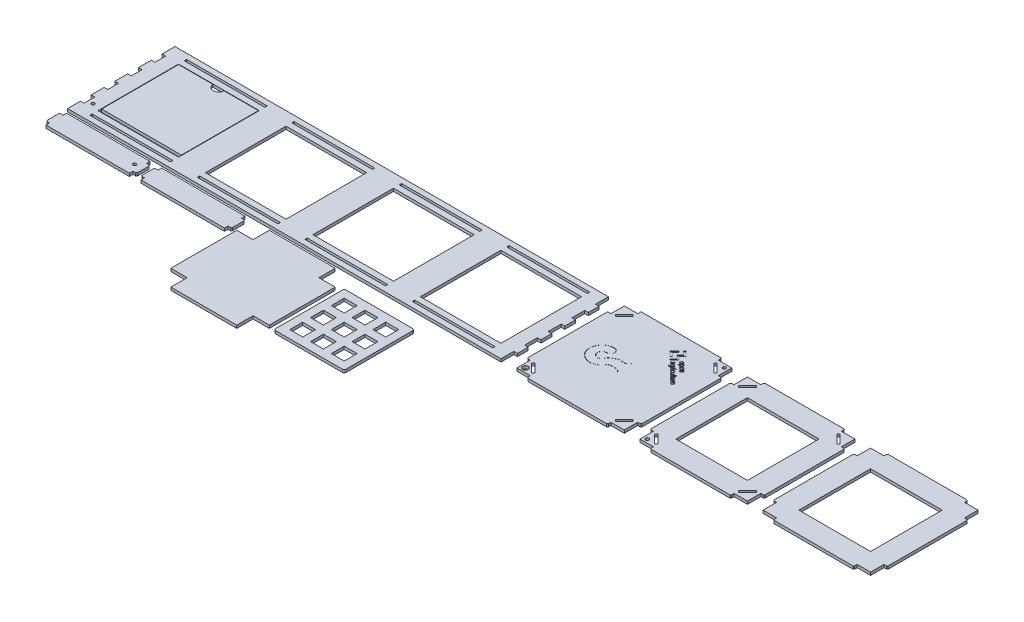
SolidWorks part; units mm, degrees
ref_plane "Front" through (0, 0, 0) normal (0, 0, 1) x (1, 0, 0)
ref_plane "Top" through (0, 0, 0) normal (0, 1, 0) x (1, 0, 0)
ref_plane "Right" through (0, 0, 0) normal (1, 0, 0) x (0, 0, -1)
sketch "Sketch1" plane through (0, 0, 0) normal (0, 1, 0) x (1, 0, 0)
  line L0 (0, 0) -> (228.6, 0) construction
  line L2 (-76.2, 76.2) -> (-76.2, -76.2) construction
  line L4 (76.2, 76.2) -> (76.2, -76.2) construction
  line L5 (-76.2, 76.2) -> (76.2, -76.2) construction
  line L6 (-76.2, -76.2) -> (76.2, 76.2) construction
  line L11 (76.2, 76.2) -> (228.6, 76.2)
  line L12 (76.2, 76.2) -> (76.2, -76.2) construction
  line L13 (76.2, -76.2) -> (228.6, -76.2)
  line L14 (228.6, 76.2) -> (228.6, -76.2) construction
  line L19 (-76.2, -76.2) -> (-228.6, -76.2)
  line L20 (-76.2, -76.2) -> (-76.2, 76.2) construction
  line L21 (-76.2, 76.2) -> (-228.6, 76.2)
  line L28 (76.2, -76.2) -> (-76.2, -76.2)
  line L34 (76.2, 76.2) -> (-76.2, 76.2)
  line L35 (-228.6, 76.2) -> (-228.6, -76.2) construction
  line L43 (-228.6, 76.2) -> (-381, 76.2)
  line L44 (-381, 76.2) -> (-381, -76.2) construction
  line L45 (-381, -76.2) -> (-228.6, -76.2)
  line L46 (228.6, 76.2) -> (228.6, 57.98)
  line L47 (228.6, 57.98) -> (233.68, 57.98)
  line L48 (233.68, 57.98) -> (233.68, 42.655)
  line L49 (233.68, 42.655) -> (228.6, 42.655)
  line L50 (228.6, 42.655) -> (228.6, 24.435)
  line L51 (228.6, 24.435) -> (233.68, 24.435)
  line L63 (233.68, 24.435) -> (233.68, 9.11)
  line L64 (233.68, 9.11) -> (228.6, 9.11)
  line L65 (228.6, 9.11) -> (228.6, -9.11)
  line L66 (228.6, -9.11) -> (233.68, -9.11)
  line L67 (233.68, -9.11) -> (233.68, -24.435)
  line L68 (233.68, -24.435) -> (228.6, -24.435)
  line L69 (228.6, -24.435) -> (228.6, -42.655)
  line L70 (228.6, -42.655) -> (233.68, -42.655)
  line L71 (233.68, -42.655) -> (233.68, -57.98)
  line L72 (233.68, -57.98) -> (228.6, -57.98)
  line L73 (228.6, -57.98) -> (228.6, -76.2)
  line L74 (-381, 76.2) -> (-386.08, 76.2)
  line L76 (-386.08, 57.9375) -> (-381, 57.9375)
  line L78 (-381, 42.6975) -> (-386.08, 42.6975)
  line L80 (-386.08, 24.3925) -> (-381, 24.3925)
  line L82 (-381, 9.1525) -> (-386.08, 9.1525)
  line L84 (-386.08, -9.1525) -> (-381, -9.1525)
  line L86 (-381, -24.3925) -> (-386.08, -24.3925)
  line L88 (-386.08, -42.6975) -> (-381, -42.6975)
  line L90 (-381, -57.9375) -> (-386.08, -57.9375)
  line L92 (-386.08, -76.2) -> (-381, -76.2)
  line L93 (233.68, 16.7725) -> (-381, 16.7725) construction
  line L94 (-381, 50.3175) -> (233.68, 50.3175) construction
  line L95 (-386.08, 76.2) -> (-386.08, 57.9375)
  line L96 (-386.08, 42.6975) -> (-386.08, 24.3925)
  line L97 (-381, 57.9375) -> (-381, 42.6975)
  line L98 (-381, 24.3925) -> (-381, 9.1525)
  line L99 (-381, -9.1525) -> (-381, -24.3925)
  line L100 (-381, -42.6975) -> (-381, -57.9375)
  line L101 (-381, -50.3175) -> (233.68, -50.3175) construction
  line L102 (-381, -16.7725) -> (233.68, -16.7725) construction
  line L103 (-386.08, 9.1525) -> (-386.08, -9.1525)
  line L104 (-386.08, -24.3925) -> (-386.08, -42.6975)
  line L105 (-386.08, -57.9375) -> (-386.08, -76.2)
  point P0 (0, 0)
  dimension "D2" = 152.4
  dimension "D1" = 152.4
  dimension "D3" = 5.08
  dimension "D5" = 15.24
  dimension "D4" = 15.325
extrude "Boss-Extrude1" add sketch "Sketch1" along normal blind 4.064
sketch "Sketch4" plane through (0, 4.064, 0) normal (0, 1, 0) x (1, 0, 0)
  line L0 (-228.6, 76.2) -> (-228.6, -76.2) construction
  line L1 (-228.6, 76.2) -> (-228.6, -76.2)
  line L2 (-76.2, 76.2) -> (-76.2, -76.2) construction
  line L3 (-76.2, 76.2) -> (-76.2, -76.2)
  line L4 (76.2, 76.2) -> (76.2, -76.2) construction
  line L5 (76.2, 76.2) -> (76.2, -76.2)
sketch "Sketch5" plane through (0, 4.064, 0) normal (0, 1, 0) x (1, 0, 0)
  line L0 (-381, -9.1525) -> (-381, 9.1525) construction
  line L1 (-228.6, 0) -> (-381, 0) construction
  line L2 (-228.6, 76.2) -> (-228.6, -76.2) construction
  line L3 (-228.6, 0) -> (-76.2, 0) construction
  line L4 (-76.2, 76.2) -> (-76.2, -76.2) construction
  line L5 (-76.2, 0) -> (76.2, 0) construction
  line L6 (76.2, 76.2) -> (76.2, -76.2) construction
  line L7 (76.2, 0) -> (228.6, 0) construction
  line L8 (228.6, -9.11) -> (228.6, 9.11) construction
  line L9 (-304.8, 0) -> (-304.8, -76.2) construction
  line L10 (-386.08, -76.2) -> (228.6, -76.2) construction
  line L11 (-152.4, 0) -> (-152.4, -76.2) construction
  line L12 (0, 0) -> (0, -76.2) construction
  line L13 (152.4, 0) -> (152.4, -76.2) construction
  line L14 (-247.65, -68.58) -> (-247.65, -76.2) construction
  line L15 (-361.95, -65.278) -> (-247.65, -65.278)
  line L16 (-361.95, -65.278) -> (-361.95, -68.58)
  line L17 (-361.95, -68.58) -> (-247.65, -68.58)
  line L18 (-247.65, -65.278) -> (-247.65, -68.58)
  line L19 (-361.95, -65.278) -> (-247.65, -68.58) construction
  line L20 (-361.95, -68.58) -> (-247.65, -65.278) construction
  line L21 (-209.55, -65.278) -> (-95.25, -65.278)
  line L22 (-209.55, -65.278) -> (-209.55, -68.58)
  line L23 (-209.55, -68.58) -> (-95.25, -68.58)
  line L24 (-95.25, -65.278) -> (-95.25, -68.58)
  line L25 (-209.55, -65.278) -> (-95.25, -68.58) construction
  line L26 (-209.55, -68.58) -> (-95.25, -65.278) construction
  line L27 (-57.15, -68.58) -> (57.15, -68.58)
  line L28 (-57.15, -68.58) -> (-57.15, -65.278)
  line L29 (-57.15, -65.278) -> (57.15, -65.278)
  line L30 (57.15, -68.58) -> (57.15, -65.278)
  line L31 (-57.15, -68.58) -> (57.15, -65.278) construction
  line L32 (-57.15, -65.278) -> (57.15, -68.58) construction
  line L33 (95.25, -68.58) -> (209.55, -68.58)
  line L34 (95.25, -68.58) -> (95.25, -65.278)
  line L35 (95.25, -65.278) -> (209.55, -65.278)
  line L36 (209.55, -68.58) -> (209.55, -65.278)
  line L37 (95.25, -68.58) -> (209.55, -65.278) construction
  line L38 (95.25, -65.278) -> (209.55, -68.58) construction
  line L39 (95.25, 65.278) -> (209.55, 68.58) construction
  line L40 (95.25, 68.58) -> (209.55, 65.278) construction
  line L41 (-57.15, 65.278) -> (57.15, 68.58) construction
  line L42 (-57.15, 68.58) -> (57.15, 65.278) construction
  line L43 (-209.55, 68.58) -> (-95.25, 65.278) construction
  line L44 (-209.55, 65.278) -> (-95.25, 68.58) construction
  line L45 (-361.95, 68.58) -> (-247.65, 65.278) construction
  line L46 (-361.95, 65.278) -> (-247.65, 68.58) construction
  line L47 (-247.65, 68.58) -> (-247.65, 76.2) construction
  line L48 (209.55, 68.58) -> (209.55, 65.278)
  line L49 (95.25, 65.278) -> (209.55, 65.278)
  line L50 (95.25, 68.58) -> (95.25, 65.278)
  line L51 (95.25, 68.58) -> (209.55, 68.58)
  line L52 (57.15, 68.58) -> (57.15, 65.278)
  line L53 (-57.15, 65.278) -> (57.15, 65.278)
  line L54 (-57.15, 68.58) -> (-57.15, 65.278)
  line L55 (-57.15, 68.58) -> (57.15, 68.58)
  line L56 (-95.25, 65.278) -> (-95.25, 68.58)
  line L57 (-209.55, 68.58) -> (-95.25, 68.58)
  line L58 (-209.55, 65.278) -> (-209.55, 68.58)
  line L59 (-209.55, 65.278) -> (-95.25, 65.278)
  line L60 (-247.65, 65.278) -> (-247.65, 68.58)
  line L61 (-361.95, 68.58) -> (-247.65, 68.58)
  line L62 (-361.95, 65.278) -> (-361.95, 68.58)
  line L63 (-361.95, 65.278) -> (-247.65, 65.278)
  line L64 (228.6, 76.2) -> (-386.08, 76.2) construction
  line L65 (-361.95, 57.15) -> (-247.65, 57.15)
  line L66 (-361.95, 57.15) -> (-361.95, -57.15)
  line L67 (-361.95, -57.15) -> (-247.65, -57.15)
  line L68 (-247.65, 57.15) -> (-247.65, -57.15)
  line L69 (-361.95, 57.15) -> (-247.65, -57.15) construction
  line L70 (-361.95, -57.15) -> (-247.65, 57.15) construction
  line L71 (-209.55, 57.15) -> (-95.25, 57.15)
  line L72 (-209.55, 57.15) -> (-209.55, -57.15)
  line L73 (-209.55, -57.15) -> (-95.25, -57.15)
  line L74 (-95.25, 57.15) -> (-95.25, -57.15)
  line L75 (-209.55, 57.15) -> (-95.25, -57.15) construction
  line L76 (-209.55, -57.15) -> (-95.25, 57.15) construction
  line L77 (-57.15, 57.15) -> (57.15, 57.15)
  line L78 (-57.15, 57.15) -> (-57.15, -57.15)
  line L79 (-57.15, -57.15) -> (57.15, -57.15)
  line L80 (57.15, 57.15) -> (57.15, -57.15)
  line L81 (-57.15, 57.15) -> (57.15, -57.15) construction
  line L82 (-57.15, -57.15) -> (57.15, 57.15) construction
  line L83 (95.25, 57.15) -> (209.55, 57.15)
  line L84 (95.25, 57.15) -> (95.25, -57.15)
  line L85 (95.25, -57.15) -> (209.55, -57.15)
  line L86 (209.55, 57.15) -> (209.55, -57.15)
  line L87 (95.25, 57.15) -> (209.55, -57.15) construction
  line L88 (95.25, -57.15) -> (209.55, 57.15) construction
  circle A0 centre (-373.95, -52.15) radius 2.2225
  point P27 (-304.8, -66.929)
  point P32 (-152.4, -66.929)
  point P37 (0, -66.929)
  point P42 (152.4, -66.929)
  point P66 (152.4, 66.929)
  point P67 (0, 66.929)
  point P68 (-152.4, 66.929)
  point P69 (-304.8, 66.929)
  dimension "D5" = 4.445
  dimension "D7" = 5
  dimension "D1" = 7.62
  dimension "D2" = 3.302
  dimension "D3" = 114.3
  dimension "D4" = 19.05
  dimension "D6" = 12
  dimension "D8" = 19.05
extrude "Cut-Extrude2" cut sketch "Sketch5" against normal through all
sketch "Sketch6" plane through (0, 0, 0) normal (0, 1, 0) x (1, 0, 0)
  line L0 (0, 0) -> (327.3425, 0) construction
  line L1 (327.3425, 0) -> (327.3425, 78.5813) construction
  line L2 (251.1425, 76.2) -> (403.5425, 76.2) construction
  line L3 (251.1425, 76.2) -> (251.1425, -76.2) construction
  line L4 (251.1425, -76.2) -> (403.5425, -76.2) construction
  line L5 (403.5425, 76.2) -> (403.5425, -76.2) construction
  line L6 (251.1425, 76.2) -> (403.5425, -76.2) construction
  line L7 (251.1425, -76.2) -> (403.5425, 76.2) construction
  line L8 (327.3425, 0) -> (405.9238, 0) construction
  line L9 (327.3425, 0) -> (327.3425, -78.5813) construction
  line L10 (251.1425, 57.185) -> (251.1425, 76.2)
  line L11 (270.1575, 80.9625) -> (384.5275, 80.9625)
  line L12 (270.1575, 80.9625) -> (270.1575, 76.2)
  line L13 (270.1575, 76.2) -> (384.5275, 76.2) construction
  line L14 (384.5275, 80.9625) -> (384.5275, 76.2)
  line L15 (270.1575, 80.9625) -> (384.5275, 76.2) construction
  line L16 (270.1575, 76.2) -> (384.5275, 80.9625) construction
  line L17 (408.305, -57.185) -> (403.5425, -57.185)
  line L18 (408.305, -57.185) -> (408.305, 57.185)
  line L19 (408.305, 57.185) -> (403.5425, 57.185)
  line L20 (403.5425, -57.185) -> (403.5425, 57.185) construction
  line L21 (408.305, -57.185) -> (403.5425, 57.185) construction
  line L22 (408.305, 57.185) -> (403.5425, -57.185) construction
  line L23 (270.1575, -80.9625) -> (384.5275, -80.9625)
  line L24 (270.1575, -80.9625) -> (270.1575, -76.2)
  line L25 (270.1575, -76.2) -> (384.5275, -76.2) construction
  line L26 (384.5275, -80.9625) -> (384.5275, -76.2)
  line L27 (270.1575, -80.9625) -> (384.5275, -76.2) construction
  line L28 (270.1575, -76.2) -> (384.5275, -80.9625) construction
  line L29 (246.38, 57.185) -> (251.1425, 57.185)
  line L30 (246.38, 57.185) -> (246.38, -57.185)
  line L31 (246.38, -57.185) -> (251.1425, -57.185)
  line L32 (251.1425, 57.185) -> (251.1425, -57.185) construction
  line L33 (246.38, 57.185) -> (251.1425, -57.185) construction
  line L34 (246.38, -57.185) -> (251.1425, 57.185) construction
  line L35 (251.1425, 76.2) -> (270.1575, 76.2)
  line L36 (384.5275, 76.2) -> (403.5425, 76.2)
  line L37 (403.5425, 76.2) -> (403.5425, 57.185)
  line L38 (403.5425, -57.185) -> (403.5425, -76.2)
  line L39 (403.5425, -76.2) -> (384.5275, -76.2)
  line L40 (270.1575, -76.2) -> (251.1425, -76.2)
  line L41 (251.1425, -76.2) -> (251.1425, -57.185)
  line L42 (421.005, 57.185) -> (421.005, -57.185)
  line L43 (421.005, 57.185) -> (425.7675, 57.185)
  line L44 (425.7675, 57.185) -> (425.7675, 76.2)
  line L45 (425.7675, 76.2) -> (444.7825, 76.2)
  line L46 (444.7825, 80.9625) -> (444.7825, 76.2)
  line L47 (444.7825, 80.9625) -> (559.1525, 80.9625)
  line L48 (559.1525, 80.9625) -> (559.1525, 76.2)
  line L49 (559.1525, 76.2) -> (578.1675, 76.2)
  line L50 (578.1675, 76.2) -> (578.1675, 57.185)
  line L51 (582.93, 57.185) -> (578.1675, 57.185)
  line L52 (582.93, -57.185) -> (582.93, 57.185)
  line L53 (582.93, -57.185) -> (578.1675, -57.185)
  line L54 (578.1675, -57.185) -> (578.1675, -76.2)
  line L55 (578.1675, -76.2) -> (559.1525, -76.2)
  line L56 (559.1525, -80.9625) -> (559.1525, -76.2)
  line L57 (444.7825, -80.9625) -> (559.1525, -80.9625)
  line L58 (444.7825, -80.9625) -> (444.7825, -76.2)
  line L59 (444.7825, -76.2) -> (425.7675, -76.2)
  line L60 (425.7675, -76.2) -> (425.7675, -57.185)
  line L61 (421.005, -57.185) -> (425.7675, -57.185)
  line L62 (425.7675, 76.2) -> (578.1675, -76.2) construction
  line L63 (595.63, 57.185) -> (595.63, -57.185)
  line L64 (595.63, 57.185) -> (600.3925, 57.185)
  line L65 (600.3925, 57.185) -> (600.3925, 76.2)
  line L66 (600.3925, 76.2) -> (619.4075, 76.2)
  line L67 (619.4075, 80.9625) -> (619.4075, 76.2)
  line L68 (619.4075, 80.9625) -> (733.7775, 80.9625)
  line L69 (733.7775, 80.9625) -> (733.7775, 76.2)
  line L70 (733.7775, 76.2) -> (752.7925, 76.2)
  line L71 (752.7925, 76.2) -> (752.7925, 57.185)
  line L72 (757.555, 57.185) -> (752.7925, 57.185)
  line L73 (757.555, -57.185) -> (757.555, 57.185)
  line L74 (757.555, -57.185) -> (752.7925, -57.185)
  line L75 (752.7925, -57.185) -> (752.7925, -76.2)
  line L76 (752.7925, -76.2) -> (733.7775, -76.2)
  line L77 (733.7775, -80.9625) -> (733.7775, -76.2)
  line L78 (619.4075, -80.9625) -> (733.7775, -80.9625)
  line L79 (619.4075, -80.9625) -> (619.4075, -76.2)
  line L80 (619.4075, -76.2) -> (600.3925, -76.2)
  line L81 (600.3925, -76.2) -> (600.3925, -57.185)
  line L82 (595.63, -57.185) -> (600.3925, -57.185)
  line L83 (600.3925, 76.2) -> (752.7925, -76.2) construction
  line L84 (451.1675, 50.8) -> (552.7675, 50.8)
  line L85 (451.1675, 50.8) -> (451.1675, -50.8)
  line L86 (451.1675, -50.8) -> (552.7675, -50.8)
  line L87 (552.7675, 50.8) -> (552.7675, -50.8)
  line L88 (451.1675, 50.8) -> (552.7675, -50.8) construction
  line L89 (451.1675, -50.8) -> (552.7675, 50.8) construction
  line L90 (233.68, -24.435) -> (233.68, -9.11) construction
  line L91 (727.3925, 50.8) -> (625.7925, 50.8)
  line L92 (727.3925, 50.8) -> (727.3925, -50.8)
  line L93 (727.3925, -50.8) -> (625.7925, -50.8)
  line L94 (625.7925, 50.8) -> (625.7925, -50.8)
  line L95 (727.3925, 50.8) -> (625.7925, -50.8) construction
  line L96 (727.3925, -50.8) -> (625.7925, 50.8) construction
  line L97 (-76.2, -57.15) -> (76.2, -57.15) construction
  line L98 (-76.2, 76.2) -> (-76.2, -76.2) construction
  line L99 (76.2, 76.2) -> (76.2, -76.2) construction
  line L100 (76.2, -57.15) -> (228.6, -57.15) construction
  line L101 (228.6, -76.2) -> (228.6, -57.98) construction
  line L102 (-57.15, -57.15) -> (57.15, -57.15) construction
  line L103 (95.25, 57.15) -> (209.55, 57.15) construction
  point P22 (248.7613, 0)
  point P67 (501.9675, 0)
  point P72 (676.5925, 0)
  dimension "D3" = 4.7625
  dimension "D7" = 12.7
  dimension "D8" = 101.6
  dimension "D5" = 12.7
  dimension "D1" = 114.3
  dimension "D2" = 114.37
  dimension "D6" = 3
extrude "Boss-Extrude2" add sketch "Sketch6" along normal blind 4.064 separate body
sketch "Sketch7" plane through (0, 0, 0) normal (0, 1, 0) x (1, 0, 0)
  line L0 (-361.95, 65.278) -> (-361.95, -53.086) construction
  line L1 (-381.08, -82.55) -> (-262.716, -82.55)
  line L2 (-381.08, -82.55) -> (-381.08, -87.63)
  line L3 (-381.08, -111.76) -> (-262.716, -111.76)
  line L4 (-262.716, -82.55) -> (-262.716, -87.63)
  line L5 (-381.08, -82.55) -> (-262.716, -111.76) construction
  line L6 (-381.08, -111.76) -> (-262.716, -82.55) construction
  line L7 (-361.95, 57.15) -> (-361.95, -57.15) construction
  line L8 (-361.95, -53.086) -> (-361.95, -57.15) construction
  line L9 (251.1425, -57.185) -> (251.1425, -76.2) construction
  line L10 (251.1425, -76.2) -> (270.1575, -76.2) construction
  line L12 (-381.08, -87.63) -> (-386.08, -87.63)
  line L13 (257.5967, -57.1734) -> (270.1691, -69.7458) construction
  line L14 (257.5967, -57.1734) -> (255.2618, -59.5083) construction
  line L15 (255.2618, -59.5083) -> (267.8342, -72.0807) construction
  line L16 (270.1691, -69.7458) -> (267.8342, -72.0807) construction
  line L17 (257.5967, -57.1734) -> (267.8342, -72.0807) construction
  line L18 (255.2618, -59.5083) -> (270.1691, -69.7458) construction
  line L19 (-386.08, -87.63) -> (-386.08, -106.68)
  line L20 (-386.08, -106.68) -> (-381.08, -106.68)
  line L22 (262.7155, -64.627) -> (260.65, -66.6925) construction
  line L23 (-381.08, -106.68) -> (-381.08, -111.76)
  line L24 (-262.716, -87.63) -> (-257.716, -87.63)
  line L25 (-257.716, -87.63) -> (-257.716, -106.68)
  line L26 (-257.716, -106.68) -> (-262.716, -106.68)
  line L27 (-262.716, -106.68) -> (-262.716, -111.76)
  line L28 (-386.08, -76.2) -> (228.6, -76.2) construction
  line L29 (-386.08, -57.9375) -> (-386.08, -76.2) construction
  line L30 (-246.366, -82.55) -> (-128.002, -82.55)
  line L31 (-246.366, -82.55) -> (-246.366, -87.63)
  line L32 (-246.366, -111.76) -> (-128.002, -111.76)
  line L33 (-128.002, -82.55) -> (-128.002, -87.63)
  line L34 (-246.366, -87.63) -> (-251.366, -87.63)
  line L35 (-251.366, -87.63) -> (-251.366, -106.68)
  line L36 (-251.366, -106.68) -> (-246.366, -106.68)
  line L37 (-246.366, -106.68) -> (-246.366, -111.76)
  line L38 (-128.002, -87.63) -> (-123.002, -87.63)
  line L39 (-123.002, -87.63) -> (-123.002, -106.68)
  line L40 (-123.002, -106.68) -> (-128.002, -106.68)
  line L41 (-128.002, -106.68) -> (-128.002, -111.76)
  line L42 (-246.366, -82.55) -> (-128.002, -111.76) construction
  line L43 (-246.366, -111.76) -> (-128.002, -82.55) construction
  line L44 (-361.95, 65.278) -> (-386.08, 65.278) construction
  line L45 (-386.08, 76.2) -> (-386.08, 57.9375) construction
  line L46 (251.1425, -57.185) -> (270.1575, -76.2) construction
  point P0 (-321.898, -97.155)
  point P14 (262.7155, -64.627)
  point P38 (-187.184, -97.155)
  dimension "D1" = 29.21
  dimension "D2" = 4.064
  dimension "D3" = 3.302
  dimension "D4" = 19.05
  dimension "D5" = 17.78
  dimension "D6" = 5
  dimension "D7" = 6.35
  dimension "D9" = 6.35
  dimension "D10" = 1.27
  dimension "D8" = 2
extrude "PILLAR POSITION" add sketch "Sketch7" along normal blind 4.064 separate body
sketch "Sketch8" plane through (0, 4.064, 0) normal (0, 1, 0) x (1, 0, 0)
  line L0 (255.2618, -59.5083) -> (267.8342, -72.0807) construction
  line L1 (270.1691, -69.7458) -> (267.8342, -72.0807) construction
  line L2 (257.5967, -57.1734) -> (270.1691, -69.7458) construction
  line L3 (257.5967, -57.1734) -> (255.2618, -59.5083) construction
  line L4 (255.2618, -59.5083) -> (267.8342, -72.0807)
  line L5 (270.1691, -69.7458) -> (267.8342, -72.0807)
  line L6 (257.5967, -57.1734) -> (270.1691, -69.7458)
  line L7 (257.5967, -57.1734) -> (255.2618, -59.5083)
  line L8 (251.1425, 76.2) -> (403.5425, -76.2) construction
  line L9 (270.1691, 69.7458) -> (257.5967, 57.1734)
  line L10 (270.1691, 69.7458) -> (267.8342, 72.0807)
  line L11 (267.8342, 72.0807) -> (255.2618, 59.5083)
  line L12 (257.5967, 57.1734) -> (255.2618, 59.5083)
  line L13 (397.0883, 57.1734) -> (384.5159, 69.7458)
  line L14 (397.0883, 57.1734) -> (399.4232, 59.5083)
  line L15 (399.4232, 59.5083) -> (386.8508, 72.0807)
  line L16 (384.5159, 69.7458) -> (386.8508, 72.0807)
  line L17 (384.5159, -69.7458) -> (397.0883, -57.1734)
  line L18 (384.5159, -69.7458) -> (386.8508, -72.0807)
  line L19 (386.8508, -72.0807) -> (399.4232, -59.5083)
  line L20 (397.0883, -57.1734) -> (399.4232, -59.5083)
  line L21 (425.7675, -57.185) -> (444.7825, -76.2) construction
  line L22 (429.8868, -59.5083) -> (432.2217, -57.1734)
  line L23 (432.2217, -57.1734) -> (444.7941, -69.7458)
  line L24 (444.7941, -69.7458) -> (442.4592, -72.0807)
  line L25 (435.275, -66.6925) -> (438.5079, -63.4596) construction
  line L26 (429.8868, -59.5083) -> (442.4592, -72.0807)
  line L27 (425.7675, 76.2) -> (578.1675, -76.2) construction
  line L28 (432.2217, 57.1734) -> (429.8868, 59.5083)
  line L29 (442.4592, 72.0807) -> (429.8868, 59.5083)
  line L30 (442.4592, 72.0807) -> (444.7941, 69.7458)
  line L31 (444.7941, 69.7458) -> (432.2217, 57.1734)
  line L32 (559.1409, 69.7458) -> (561.4758, 72.0807)
  line L33 (574.0482, 59.5083) -> (561.4758, 72.0807)
  line L34 (574.0482, 59.5083) -> (571.7133, 57.1734)
  line L35 (571.7133, 57.1734) -> (559.1409, 69.7458)
  line L36 (571.7133, -57.1734) -> (574.0482, -59.5083)
  line L37 (561.4758, -72.0807) -> (574.0482, -59.5083)
  line L38 (561.4758, -72.0807) -> (559.1409, -69.7458)
  line L39 (559.1409, -69.7458) -> (571.7133, -57.1734)
  line L40 (251.1425, -57.185) -> (270.1575, -76.2) construction
  line L41 (261.548, -65.7945) -> (260.65, -66.6925) construction
  line L42 (442.4592, -72.0807) -> (441.5612, -72.9787) construction
  circle A0 centre (327.3425, 0) radius 20.7898 construction
  circle A1 centre (327.3425, 0) radius 20.7898 construction
  circle A2 centre (327.3425, 0) radius 20.7898 construction
  circle A3 centre (327.3425, 0) radius 20.7898 construction
  circle A4 centre (501.9675, 0) radius 71.842 construction
  point P28 (327.3425, 0)
  point P58 (501.9675, 0)
  dimension "D1" = 4
  dimension "D2" = 4
extrude "Cut-Extrude3" cut sketch "Sketch8" against normal through all
sketch "Sketch10" plane through (0, 4.064, 0) normal (0, 1, 0) x (1, 0, 0)
  line L0 (-247.65, 57.15) -> (-361.95, 57.15) construction
  line L1 (-95.25, 57.15) -> (-209.55, 57.15) construction
  line L2 (57.15, 57.15) -> (-57.15, 57.15) construction
  line L3 (209.55, 57.15) -> (95.25, 57.15) construction
  line L4 (-296.8, 57.15) -> (-312.8, 57.15)
  line L5 (-144.4, 57.15) -> (-160.4, 57.15)
  line L6 (8, 57.15) -> (-8, 57.15)
  line L7 (160.4, 57.15) -> (144.4, 57.15)
  line L8 (-361.95, -53.086) -> (-247.65, -53.086)
  line L9 (-304.8, -53.086) -> (-304.8, -57.15) construction
  line L14 (-361.95, 57.15) -> (-361.95, -57.15) construction
  line L15 (-247.65, -57.15) -> (-247.65, 57.15) construction
  line L16 (-361.95, -57.15) -> (-247.65, -57.15) construction
  line L17 (-209.55, -53.086) -> (-95.25, -53.086)
  line L18 (-209.55, 57.15) -> (-209.55, -57.15) construction
  line L19 (-95.25, -57.15) -> (-95.25, 57.15) construction
  line L20 (-57.15, -53.086) -> (57.15, -53.086)
  line L21 (-57.15, 57.15) -> (-57.15, -57.15) construction
  line L22 (57.15, -57.15) -> (57.15, 57.15) construction
  line L23 (95.25, -53.086) -> (209.55, -53.086)
  line L24 (95.25, 57.15) -> (95.25, -57.15) construction
  line L25 (209.55, -57.15) -> (209.55, 57.15) construction
  line L27 (-361.95, 57.15) -> (-361.95, -53.086) construction
  arc A0 (-312.8, 57.15) -> (-296.8, 57.15) centre (-304.8, 57.15) ccw
  arc A1 (-160.4, 57.15) -> (-144.4, 57.15) centre (-152.4, 57.15) ccw
  arc A2 (-8, 57.15) -> (8, 57.15) centre (0, 57.15) ccw
  arc A3 (144.4, 57.15) -> (160.4, 57.15) centre (152.4, 57.15) ccw
  dimension "D1" = 16
  dimension "D2" = 4.064
sketch "Sketch18" plane through (0, 4.064, 0) normal (0, 1, 0) x (1, 0, 0)
  line L0 (-361.95, 57.15) -> (-247.65, -53.086) construction
  line L6 (-247.65, 57.15) -> (-361.95, 57.15) construction
  line L7 (-361.3901, 56.61) -> (-312.7818, 56.61)
  line L9 (-361.3901, 56.61) -> (-361.3901, -52.546)
  line L10 (-361.3901, -52.546) -> (-248.2099, -52.546)
  line L11 (-248.2099, 56.61) -> (-248.2099, -52.546)
  line L12 (-361.3901, 56.61) -> (-248.2099, -52.546) construction
  line L13 (-361.3901, -52.546) -> (-248.2099, 56.61) construction
  line L14 (-296.8182, 56.61) -> (-248.2099, 56.61)
  arc A2 (-312.8, 57.15) -> (-296.8, 57.15) centre (-304.8, 57.15) ccw construction
  arc A3 (-312.7818, 56.61) -> (-296.8182, 56.61) centre (-304.8, 57.15) ccw
  point P4 (-304.8, 2.032)
  dimension "D1" = 0.54
extrude "Boss-Extrude8" add sketch "Sketch18" against normal blind 4.064 separate body
sketch "Sketch11" plane through (0, 0, 0) normal (0, 1, 0) x (1, 0, 0)
  line L0 (-209.55, -57.15) -> (-209.55, -65.278) construction
  line L5 (-93.538, -105.664) -> (-0.066, -105.664) construction
  line L6 (-93.538, -105.664) -> (-93.538, -199.136) construction
  line L7 (-93.538, -199.136) -> (-0.066, -199.136) construction
  line L8 (-0.066, -105.664) -> (-0.066, -199.136) construction
  line L9 (-93.538, -105.664) -> (-0.066, -199.136) construction
  line L10 (-93.538, -199.136) -> (-0.066, -105.664) construction
  line L11 (-93.538, -105.664) -> (-116.652, -105.664)
  line L12 (-116.652, -105.664) -> (-116.652, -199.136)
  line L13 (-116.652, -199.136) -> (-93.538, -199.136)
  line L14 (-93.538, -105.664) -> (-93.538, -82.55)
  line L15 (-93.538, -82.55) -> (-0.066, -82.55)
  line L16 (-0.066, -82.55) -> (-0.066, -105.664)
  line L17 (-0.066, -105.664) -> (23.048, -105.664)
  line L18 (23.048, -105.664) -> (23.048, -199.136)
  line L19 (23.048, -199.136) -> (-0.066, -199.136)
  line L20 (-0.066, -199.136) -> (-0.066, -222.25)
  line L21 (-0.066, -222.25) -> (-93.538, -222.25)
  line L22 (-93.538, -222.25) -> (-93.538, -199.136)
  line L23 (-386.08, -76.2) -> (228.6, -76.2) construction
  line L24 (-123.002, -106.68) -> (-123.002, -87.63) construction
  line L25 (-209.55, -57.15) -> (-95.25, -57.15) construction
  line L26 (451.1675, -50.8) -> (552.7675, -50.8) construction
  line L27 (209.55, -53.086) -> (209.55, -76.2) construction
  line L28 (-97.602, -219.71) -> (3.998, -219.71) construction
  line L29 (-46.802, -152.4) -> (-46.802, -219.71) construction
  line L30 (-97.602, -219.71) -> (-97.602, -222.25) construction
  line L31 (-97.602, -222.25) -> (-93.538, -222.25) construction
  line L32 (-0.066, -222.25) -> (3.998, -222.25) construction
  line L33 (3.998, -222.25) -> (3.998, -219.71) construction
  point P0 (-46.802, -152.4)
  point P33 (-46.802, -219.71)
  dimension "D1" = 4.064
  dimension "D2" = 101.6
  dimension "D3" = 101.6
  dimension "D4" = 6.35
  dimension "D5" = 6.35
  dimension "D6" = 2.54
extrude "Boss-Extrude5" add sketch "Sketch11" along normal blind 4.064 separate body
sketch "Sketch12" plane through (0, 4.064, 0) normal (0, 1, 0) x (1, 0, 0)
  line L0 (-93.538, -105.664) -> (-0.066, -105.664)
  line L1 (-0.066, -105.664) -> (-0.066, -199.136)
  line L2 (-0.066, -199.136) -> (-93.538, -199.136)
  line L3 (-93.538, -105.664) -> (-93.538, -199.136)
sketch "Sketch13" plane through (0, 0, 0) normal (0, 1, 0) x (1, 0, 0)
  line L16 (-223.9443, 14.6616) -> (-211.1797, 14.6616)
  line L17 (-211.1797, 14.6616) -> (-211.1797, 5.1786)
  line L18 (-211.1797, 5.1786) -> (-201.7193, 5.1786)
  line L19 (350.3041, 64.4565) -> (356.7512, 58.0094)
  line L20 (356.7512, 58.0094) -> (351.9616, 53.2197)
  line L21 (351.9616, 53.2197) -> (356.7398, 48.4415)
  line L22 (356.7398, 48.4415) -> (350.2812, 41.983)
  line L24 (348.6694, 43.5948) -> (353.4934, 48.4187)
  line L25 (353.4934, 48.4187) -> (348.7266, 53.1854)
  line L26 (348.7266, 53.1854) -> (353.5391, 57.9979)
  line L27 (353.5391, 57.9979) -> (348.6923, 62.8447)
  line L28 (348.6923, 62.8447) -> (350.3041, 64.4565)
  line L29 (345.5145, 59.6669) -> (347.1377, 58.0437)
  line L30 (347.1377, 58.0437) -> (342.3023, 53.2083)
  line L31 (342.3023, 53.2083) -> (347.1262, 48.3844)
  line L32 (347.1262, 48.3844) -> (345.503, 46.7612)
  line L33 (345.503, 46.7612) -> (339.0559, 53.2083)
  line L34 (339.0559, 53.2083) -> (345.5145, 59.6669)
  line L36 (350.7409, 41.9187) -> (377.6929, 14.9667) construction
  line L37 (358.5912, 47.064) -> (396.3306, 9.3246) construction
  line L38 (348.6694, 43.5948) -> (350.2812, 41.983)
  line L41 (-201.7193, 5.1786) -> (-201.7193, -7.6086)
  line L43 (-204.9105, -7.6086) -> (-204.9105, 1.9422)
  line L44 (-204.9105, 1.9422) -> (-214.3482, 1.9422)
  line L45 (-214.3482, 1.9422) -> (-214.3482, 11.4705)
  line L46 (-214.3482, 11.4705) -> (-223.9443, 11.4705)
  line L47 (-223.9443, 11.4705) -> (-223.9443, 14.6616)
  line L48 (-223.9443, 5.1786) -> (-220.7305, 5.1786)
  line L49 (-220.7305, 5.1786) -> (-220.7305, -4.3949)
  line L50 (-220.7305, -4.3949) -> (-211.1797, -4.3949)
  line L51 (-211.1797, -4.3949) -> (-211.1797, -7.6086)
  line L52 (-211.1797, -7.6086) -> (-223.9443, -7.6086)
  line L53 (-223.9443, -7.6086) -> (-223.9443, 5.1786)
  line L54 (-200.854, -7.608) -> (-149.188, -7.608) construction
  line L55 (-361.95, 57.15) -> (-247.65, -53.086) construction
  line L56 (-204.9105, -7.6086) -> (-201.7193, -7.6086)
  line L57 (-200.854, -7.608) -> (-200.854, 5.1786) construction
  line L58 (-200.854, 5.1786) -> (-201.7193, 5.1786) construction
  line L59 (-200.854, 1.9422) -> (-182.9615, 1.9422) construction
  line L60 (-200.854, -2.3557) -> (-181.4784, -2.3557) construction
  line L61 (-361.95, 57.15) -> (-361.95, -57.15) construction
  line L62 (-273.05, 31.75) -> (-336.55, 31.75) construction
  line L63 (-273.05, 31.75) -> (-273.05, -27.686) construction
  line L64 (-273.05, -27.686) -> (-336.55, -27.686) construction
  line L65 (-336.55, 31.75) -> (-336.55, -27.686) construction
  line L66 (-273.05, 31.75) -> (-336.55, -27.686) construction
  line L67 (-273.05, -27.686) -> (-336.55, 31.75) construction
  line L68 (-247.65, 57.15) -> (-361.95, 57.15) construction
  line L69 (-361.95, -53.086) -> (-247.65, -53.086) construction
  line L70 (-247.65, -57.15) -> (-247.65, 57.15) construction
  text T0 "mit" font "Arial" height in points 18
  text T1 "media" font "Arial" height in points 18
  text T2 "lab" font "Arial" height in points 18
  text T3 "open" font "Arial" height in points 24
  text T4 " agriculture" font "Arial" height in points 24
  point P56 (-194.7375, 4.459)
  dimension "D1" = 25.4
  dimension "D4" = 25.4
  dimension "D5" = 25.4
  dimension "D6" = 25.4
sketch "Sketch14" plane through (0, 4.064, 0) normal (0, 1, 0) x (1, 0, 0)
  line L0 (-257.716, -97.155) -> (-269.9385, -97.155) construction
  line L1 (-257.716, -106.68) -> (-257.716, -87.63) construction
  circle A0 centre (-269.9385, -97.155) radius 2.2225
  circle A1 centre (-373.95, -52.15) radius 2.2225 construction
  dimension "D1" = 10
extrude "Cut-Extrude4" cut sketch "Sketch14" against normal through all
sketch "Sketch15" plane through (0, 4.064, 0) normal (0, 1, 0) x (1, 0, 0)
  line L0 (251.1425, -76.2) -> (261.548, -65.7945) construction
  line L1 (255.2618, -59.5083) -> (267.8342, -72.0807) construction
  line L2 (257.2379, -76.2006) -> (257.2379, -76.2) construction
  line L3 (251.1425, -76.2) -> (270.1575, -76.2) construction
  line L4 (261.548, -65.7945) -> (261.5484, -65.7941) construction
  line L5 (251.1425, 76.2) -> (403.5425, -76.2) construction
  line L6 (403.5425, 76.2) -> (393.137, 65.7945) construction
  line L7 (399.4232, 59.5083) -> (386.8508, 72.0807) construction
  line L8 (436.173, -65.7945) -> (425.7675, -76.2) construction
  line L9 (429.8868, -59.5083) -> (442.4592, -72.0807) construction
  circle A0 centre (257.2379, -70.1046) radius 3.95
  circle A1 centre (257.2379, -70.1046) radius 6.096 construction
  circle A2 centre (398.3397, 70.9972) radius 2.2225
  circle A3 centre (-269.9385, -97.155) radius 2.2225 construction
  circle A4 centre (430.9703, -70.9972) radius 2.413
  dimension "D1" = 7.9
  dimension "D2" = 12.192
  dimension "D3" = 4.826
extrude "Cut-Extrude5" cut sketch "Sketch15" against normal through all
sketch "Sketch16" plane through (0, 4.064, 0) normal (0, 1, 0) x (1, 0, 0)
  line L0 (451.1675, 50.8) -> (451.1675, -50.8) construction
  line L1 (454.3425, 19.05) -> (481.6251, 19.05) construction
  line L2 (454.3425, 38.1) -> (492.4425, 38.1)
  line L3 (454.3425, 38.1) -> (454.3425, 0)
  line L4 (454.3425, 0) -> (492.4425, 0)
  line L6 (454.3425, 38.1) -> (492.4425, 0) construction
  line L7 (454.3425, 0) -> (492.4425, 38.1) construction
  line L8 (481.6251, 19.05) -> (473.3925, 19.05) construction
  line L9 (492.4425, 38.1) -> (492.4425, 21.4244)
  line L10 (496.8573, 24.6016) -> (496.7727, 24.7481)
  line L11 (473.3925, 38.1) -> (473.3925, 0) construction
  line L12 (486.0925, 24.13) -> (476.6945, 24.13)
  line L13 (486.0925, 13.97) -> (476.6945, 13.97)
  line L14 (473.3925, 24.13) -> (473.3925, 13.97) construction
  line L15 (496.5065, 24.13) -> (473.3925, 24.13) construction
  line L16 (496.5065, 13.97) -> (473.3925, 13.97) construction
  line L17 (489.2958, 23.2628) -> (493.9567, 20.5397)
  line L18 (496.5065, 19.05) -> (495.7837, 19.05) construction
  line L19 (496.5065, 19.05) -> (473.3925, 19.05) construction
  line L20 (511.7626, 19.05) -> (495.7837, 19.05) construction
  line L21 (486.0925, 24.13) -> (486.0925, 13.97) construction
  line L22 (492.4425, -9.6369) -> (492.4425, 0)
  line L23 (552.7675, 50.8) -> (451.1675, 50.8) construction
  line L24 (473.3925, 27.432) -> (473.3925, 27.94) construction
  line L25 (473.3925, 10.668) -> (473.3925, 10.16) construction
  line L26 (473.3925, 27.432) -> (473.3925, 10.668)
  arc A1 (496.8967, 17.4306) -> (500.1843, 22.6039) centre (500.0625, 19.05) ccw
  arc A3 (500.3273, 30.7471) -> (496.7727, 24.7481) centre (500.2368, 26.7481) ccw
  arc A4 (496.8573, 24.6016) -> (500.1843, 22.6039) centre (500.3214, 26.6016) ccw
  arc A5 (489.2958, 23.2628) -> (486.0925, 24.13) centre (486.0925, 17.78) ccw
  arc A6 (491.0071, 11.6411) -> (486.0925, 13.97) centre (486.0925, 7.62) ccw
  arc A7 (496.8967, 17.4306) -> (493.9567, 20.5397) centre (490.1127, 13.9603) ccw
  arc A8 (476.6945, 13.97) -> (473.3925, 10.668) centre (476.6945, 10.668) ccw
  arc A9 (473.3925, 27.432) -> (476.6945, 24.13) centre (476.6945, 27.432) ccw
  arc A10 (491.0071, 11.6411) -> (500.3273, 30.7471) centre (500.0625, 19.05) ccw
  point P4 (473.3925, 19.05)
  point P28 (371.8905, 14.7821)
  dimension "D7" = 4
  dimension "D8" = 6.35
  dimension "D9" = 6.35
  dimension "D10" = 7.62
  dimension "D12" = 7.112
  dimension "D17" = 3.302
  dimension "D1" = 38.1
  dimension "D2" = 38.1
  dimension "D3" = 12.7
  dimension "D4" = 5.08
  dimension "D6" = 30
  dimension "D11" = 26.67
  dimension "D13" = 3.175
  dimension "D14" = 12.7
  dimension "D15" = 3.81
  dimension "D16" = 3.81
  dimension "D5" = 5.08
sketch "Sketch17" plane through (0, 4.064, 0) normal (0, 1, 0) x (1, 0, 0)
  line L1 (327.3425, 80.9625) -> (327.3425, -80.9625) construction
  line L12 (384.5275, 80.9625) -> (270.1575, 80.9625) construction
  line L13 (270.1575, -80.9625) -> (384.5275, -80.9625) construction
  line L30 (327.3425, 10.16) -> (327.3425, -10.16) construction
  line L31 (295.5925, 0) -> (359.0925, 0) construction
  line L32 (305.0305, 2.1893) -> (310.1105, 5.1321)
  line L34 (322.4238, -6.35) -> (314.6425, -6.35)
  line L35 (314.6425, 6.35) -> (322.4238, 6.35)
  arc A9 (310.1105, 5.1321) -> (314.6425, 6.35) centre (314.6425, -2.6913) cw
  arc A10 (301.6187, -2.0019) -> (305.0305, 2.1893) centre (308.8501, -4.4043) cw
  arc A11 (301.6187, -2.0019) -> (295.8598, 6.3444) centre (295.5925, 0) cw
  arc A14 (310.4981, -8.7261) -> (296.3195, 17.2567) centre (295.5925, 0) cw
  arc A15 (310.4981, -8.7261) -> (314.6425, -6.35) centre (314.6425, -11.1524) cw
  arc A16 (322.4238, -6.35) -> (327.3425, -10.16) centre (322.4238, -11.43) cw
  arc A17 (327.3425, 10.16) -> (322.4238, 6.35) centre (322.4238, 11.43) cw
  arc A36 (296.3195, 17.2567) -> (295.8598, 6.3444) centre (296.0896, 11.8005) cw
  point P43 (327.3425, 0)
  point P64 (327.3425, 0)
  dimension "D4" = 17.272
  dimension "D5" = 12.7
  dimension "D6" = 5.08
  dimension "D2" = 31.75
  dimension "D3" = 6.35
  dimension "D8" = 0.4971
  dimension "D9" = 7.62
  dimension "D7" = 20.32
  dimension "D10" = 5.08
  dimension "D11" = 12.7
  dimension "D12" = 30.084
extrude "Cut-Extrude-Thin1" cut sketch "Sketch17" against normal through all thin contours A16 L34 A15 A14 A36 A11 A10 L32 A9 L35 A17 thin type one direction wall 0.25
extrude "Cut-Extrude6" cut sketch "Sketch13" against normal blind 1.27 from surface starting at face at (-304.8, 4.064, -18.9813)
sketch "Sketch19" plane through (0, 4.064, 0) normal (0, 1, 0) x (1, 0, 0)
  line L0 (35.748, -105.664) -> (135.57, -205.486) construction
  line L1 (38.288, -105.664) -> (133.03, -105.664)
  line L2 (35.748, -108.204) -> (35.748, -202.946)
  line L3 (38.288, -205.486) -> (133.03, -205.486)
  line L4 (135.57, -108.204) -> (135.57, -202.946)
  line L6 (56.195, -126.111) -> (115.123, -126.111) construction
  line L7 (56.195, -126.111) -> (56.195, -185.039) construction
  line L8 (56.195, -185.039) -> (115.123, -185.039) construction
  line L9 (115.123, -126.111) -> (115.123, -185.039) construction
  line L10 (56.195, -126.111) -> (115.123, -185.039) construction
  line L11 (56.195, -185.039) -> (115.123, -126.111) construction
  line L12 (23.048, -105.664) -> (23.048, -199.136) construction
  line L13 (23.048, -105.664) -> (-0.066, -105.664) construction
  line L14 (76.515, -116.967) -> (94.803, -116.967)
  line L15 (105.979, -116.967) -> (124.267, -116.967)
  line L16 (105.979, -116.967) -> (105.979, -135.255)
  line L17 (105.979, -135.255) -> (124.267, -135.255)
  line L18 (124.267, -116.967) -> (124.267, -135.255)
  line L19 (105.979, -116.967) -> (124.267, -135.255) construction
  line L20 (105.979, -135.255) -> (124.267, -116.967) construction
  line L21 (65.339, -116.967) -> (47.051, -116.967)
  line L22 (65.339, -116.967) -> (65.339, -135.255)
  line L23 (65.339, -135.255) -> (47.051, -135.255)
  line L24 (47.051, -116.967) -> (47.051, -135.255)
  line L25 (65.339, -116.967) -> (47.051, -135.255) construction
  line L26 (65.339, -135.255) -> (47.051, -116.967) construction
  line L27 (47.051, -175.895) -> (65.339, -175.895)
  line L28 (47.051, -175.895) -> (47.051, -194.183)
  line L29 (47.051, -194.183) -> (65.339, -194.183)
  line L30 (65.339, -175.895) -> (65.339, -194.183)
  line L31 (47.051, -175.895) -> (65.339, -194.183) construction
  line L32 (47.051, -194.183) -> (65.339, -175.895) construction
  line L33 (105.979, -175.895) -> (124.267, -175.895)
  line L34 (105.979, -175.895) -> (105.979, -194.183)
  line L35 (105.979, -194.183) -> (124.267, -194.183)
  line L36 (124.267, -175.895) -> (124.267, -194.183)
  line L37 (105.979, -175.895) -> (124.267, -194.183) construction
  line L38 (105.979, -194.183) -> (124.267, -175.895) construction
  line L39 (76.515, -116.967) -> (76.515, -135.255)
  line L40 (76.515, -135.255) -> (94.803, -135.255)
  line L41 (94.803, -116.967) -> (94.803, -135.255)
  line L42 (76.515, -116.967) -> (94.803, -135.255) construction
  line L43 (76.515, -135.255) -> (94.803, -116.967) construction
  line L44 (47.051, -146.431) -> (65.339, -146.431)
  line L45 (47.051, -146.431) -> (47.051, -164.719)
  line L46 (47.051, -164.719) -> (65.339, -164.719)
  line L47 (65.339, -146.431) -> (65.339, -164.719)
  line L48 (47.051, -146.431) -> (65.339, -164.719) construction
  line L49 (47.051, -164.719) -> (65.339, -146.431) construction
  line L50 (76.515, -175.895) -> (94.803, -175.895)
  line L51 (76.515, -175.895) -> (76.515, -194.183)
  line L52 (76.515, -194.183) -> (94.803, -194.183)
  line L53 (94.803, -175.895) -> (94.803, -194.183)
  line L54 (76.515, -175.895) -> (94.803, -194.183) construction
  line L55 (76.515, -194.183) -> (94.803, -175.895) construction
  line L56 (105.979, -146.431) -> (124.267, -146.431)
  line L57 (105.979, -146.431) -> (105.979, -164.719)
  line L58 (105.979, -164.719) -> (124.267, -164.719)
  line L59 (124.267, -146.431) -> (124.267, -164.719)
  line L60 (105.979, -146.431) -> (124.267, -164.719) construction
  line L61 (105.979, -164.719) -> (124.267, -146.431) construction
  line L62 (76.515, -146.431) -> (94.803, -146.431)
  line L63 (76.515, -146.431) -> (76.515, -164.719)
  line L64 (76.515, -164.719) -> (94.803, -164.719)
  line L65 (94.803, -146.431) -> (94.803, -164.719)
  line L66 (76.515, -146.431) -> (94.803, -164.719) construction
  line L67 (76.515, -164.719) -> (94.803, -146.431) construction
  arc A0 (135.57, -108.204) -> (133.03, -105.664) centre (133.03, -108.204) ccw
  arc A1 (135.57, -202.946) -> (133.03, -205.486) centre (133.03, -202.946) cw
  arc A2 (38.288, -205.486) -> (35.748, -202.946) centre (38.288, -202.946) cw
  arc A3 (38.288, -105.664) -> (35.748, -108.204) centre (38.288, -108.204) ccw
  point P4 (85.659, -155.575)
  point P31 (85.659, -126.111)
  point P36 (56.195, -155.575)
  point P41 (85.659, -185.039)
  point P46 (115.123, -155.575)
  point P51 (85.659, -155.575)
  point P58 (135.57, -105.664)
  dimension "D7" = 2.54
  dimension "D1" = 93.472
  dimension "D2" = 99.822
  dimension "D3" = 12.7
  dimension "D4" = 18.288
  dimension "D5" = 40.64
  dimension "D6" = 11.303
extrude "Boss-Extrude9" add sketch "Sketch19" along normal blind 4.064 separate body
chamfer "Chamfer1" distance 1.27 angle 45 8 edges at (246.38, 2.032, -57.185) (246.38, 2.032, 57.185) (270.1575, 2.032, 80.9625) (384.5275, 2.032, 80.9625) (408.305, 2.032, 57.185) (408.305, 2.032, -57.185) (384.5275, 2.032, -80.9625) (270.1575, 2.032, -80.9625)
chamfer "Chamfer2" distance 1.25 angle 45 8 edges at (582.93, 2.032, -57.185) (559.1525, 2.032, -80.9625) (582.93, 2.032, 57.185) (559.1525, 2.032, 80.9625) (444.7825, 2.032, 80.9625) (421.005, 2.032, 57.185) (421.005, 2.032, -57.185) (444.7825, 2.032, -80.9625)
chamfer "Chamfer3" distance 1.25 angle 45 8 edges at (757.555, 2.032, -57.185) (757.555, 2.032, 57.185) (733.7775, 2.032, 80.9625) (619.4075, 2.032, 80.9625) (595.63, 2.032, 57.185) (733.7775, 2.032, -80.9625) (595.63, 2.032, -57.185) (619.4075, 2.032, -80.9625)
chamfer "Chamfer4" distance 1.25 angle 45 4 edges at (-257.716, 2.032, 106.68) (-257.716, 2.032, 87.63) (-386.08, 2.032, 106.68) (-386.08, 2.032, 87.63)
chamfer "Chamfer5" distance 1.25 angle 45 4 edges at (-123.002, 2.032, 87.63) (-123.002, 2.032, 106.68) (-251.366, 2.032, 106.68) (-251.366, 2.032, 87.63)
equation "\"D2@Sketch6\"=\"D1@Sketch6\"+.07"
equation "\"D4@Sketch1\"=\"D5@Sketch1\"+.085"
equation "\"D2@Sketch19\"=\"D1@Sketch19\"+.25in"
